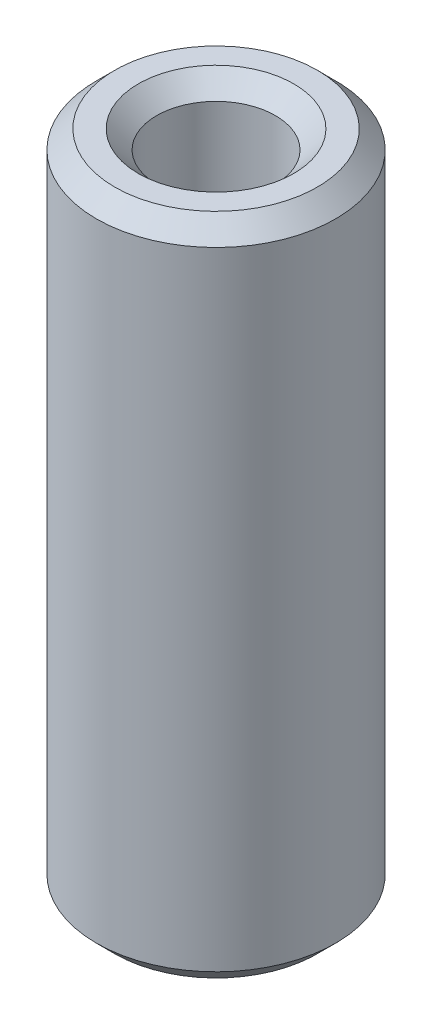
SolidWorks part; units mm, degrees
ref_plane "Front Plane" through (0, 0, 0) normal (0, 0, 1) x (1, 0, 0)
ref_plane "Top Plane" through (0, 0, 0) normal (0, 1, 0) x (1, 0, 0)
ref_plane "Right Plane" through (0, 0, 0) normal (1, 0, 0) x (0, 0, -1)
sketch "Sketch1" plane through (0, 0, 0) normal (0, 1, 0) x (1, 0, 0)
  circle A0 centre (0, 0) radius 25
  dimension "SLEEVE_OD" = 50
extrude "Boss-Extrude1" add sketch "Sketch1" along normal blind 138.7666
sketch "Sketch2" plane through (0, 0, 0) normal (0, 1, 0) x (1, 0, 0)
  circle A0 centre (0, 0) radius 12.4144
  dimension "BORE_D" = 24.8288
extrude "Cut-Extrude1" cut sketch "Sketch2" along normal through all
chamfer "Chamfer1" distance 3.8309 angle 45 4 edges at (0, 138.7666, 12.4144) (0, 0, 12.4144) (0, 0, 25) (0, 138.7666, 25)
